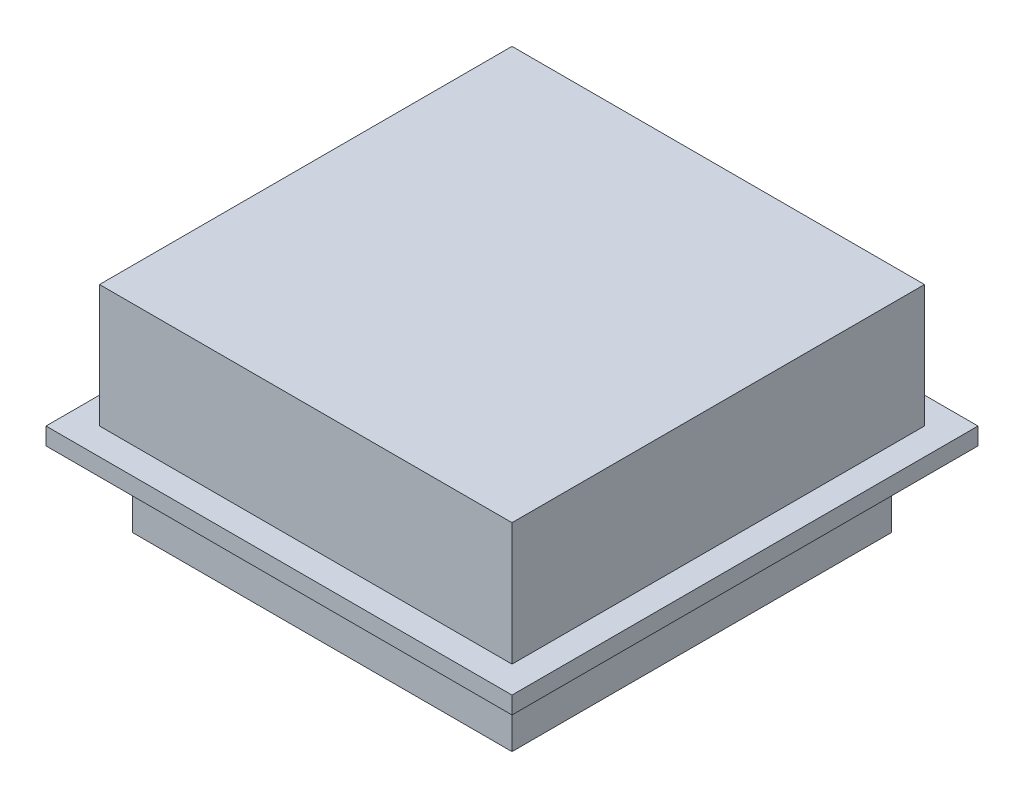
SolidWorks part; units mm, degrees
ref_plane "Front Plane" through (0, 0, 0) normal (0, 0, 1) x (1, 0, 0)
ref_plane "Top Plane" through (0, 0, 0) normal (0, 1, 0) x (1, 0, 0)
ref_plane "Right Plane" through (0, 0, 0) normal (1, 0, 0) x (0, 0, -1)
sketch "Sketch1" plane through (0, 0, 0) normal (0, 1, 0) x (1, 0, 0)
  line L1 (-5.975, -5.975) -> (5.975, -5.975)
  line L2 (-5.975, -5.975) -> (-5.975, 5.975)
  line L3 (-5.975, 5.975) -> (5.975, 5.975)
  line L4 (5.975, -5.975) -> (5.975, 5.975)
  line L5 (-5.975, -5.975) -> (5.975, 5.975) construction
  line L6 (-5.975, 5.975) -> (5.975, -5.975) construction
  point P0 (0, 0)
  dimension "D1" = 11.95
extrude "Boss-Extrude1" add sketch "Sketch1" along normal blind 3.55
sketch "Sketch2" plane through (0, 0, 0) normal (0, 1, 0) x (1, 0, 0)
  line L1 (-6.75, -6.75) -> (6.75, -6.75)
  line L2 (-6.75, -6.75) -> (-6.75, 6.75)
  line L3 (-6.75, 6.75) -> (6.75, 6.75)
  line L4 (6.75, -6.75) -> (6.75, 6.75)
  line L5 (-6.75, -6.75) -> (6.75, 6.75) construction
  line L6 (-6.75, 6.75) -> (6.75, -6.75) construction
  point P0 (0, 0)
  dimension "D1" = 13.5
extrude "Boss-Extrude2" add sketch "Sketch2" against normal blind 0.5
sketch "Sketch3" plane through (0, -0.5, 0) normal (0, -1, 0) x (1, 0, 0)
  line L1 (-5.5, 5.5) -> (5.5, 5.5)
  line L2 (-5.5, 5.5) -> (-5.5, -5.5)
  line L3 (-5.5, -5.5) -> (5.5, -5.5)
  line L4 (5.5, 5.5) -> (5.5, -5.5)
  line L5 (-5.5, 5.5) -> (5.5, -5.5) construction
  line L6 (-5.5, -5.5) -> (5.5, 5.5) construction
  point P0 (0, 0)
  dimension "D1" = 11
extrude "Boss-Extrude3" add sketch "Sketch3" along normal blind 2.17
chamfer "Chamfer1" distance 1 angle 45 2 edges at (5.5, -0.5, 0) (-5.5, -0.5, 0)
sketch "Sketch4" plane through (0, 0, -5.5) normal (0, 0, -1) x (-1, 0, 0)
  line L0 (-6.75, -0.5) -> (6.75, -0.5) construction
  line L1 (5.5, -2.67) -> (5.5, -1.5) construction
  circle A0 centre (4.94, -1.25) radius 0.56
  point P2 (4.3492, -1.2736)
  point P3 (4.5779, -1.2014)
  point P4 (4.8463, -1.1166)
  point P7 (4.8094, -1.25)
  dimension "D1" = 1.12
  dimension "D2" = 0.75
sketch3d "3DSketch1"
  spline S0 degree 2 poles (-4.94, -1.25, -5.5) (-5.3411, -1.9681, -12.6341) (1.5963, -4.6795, -9.9093) knots 0 0 0 1 1 1
  point P2 (0.2861, -4.1105, -8.6314)
  point P4 (-0.1178, -2.0003, -9.2354)
  point P5 (2.6022, -4.6795, -8.0678)
  point P7 (-0.4477, -2.2264, -9.2992)
  point P8 (-3.945, -2.2264, -9.7944)
  point P9 (2.7415, -4.6795, -8.1761)
  point P10 (1.5963, -4.6795, -9.9093)
sweep "Sweep1" add profiles "Sketch4" path "3DSketch1"
